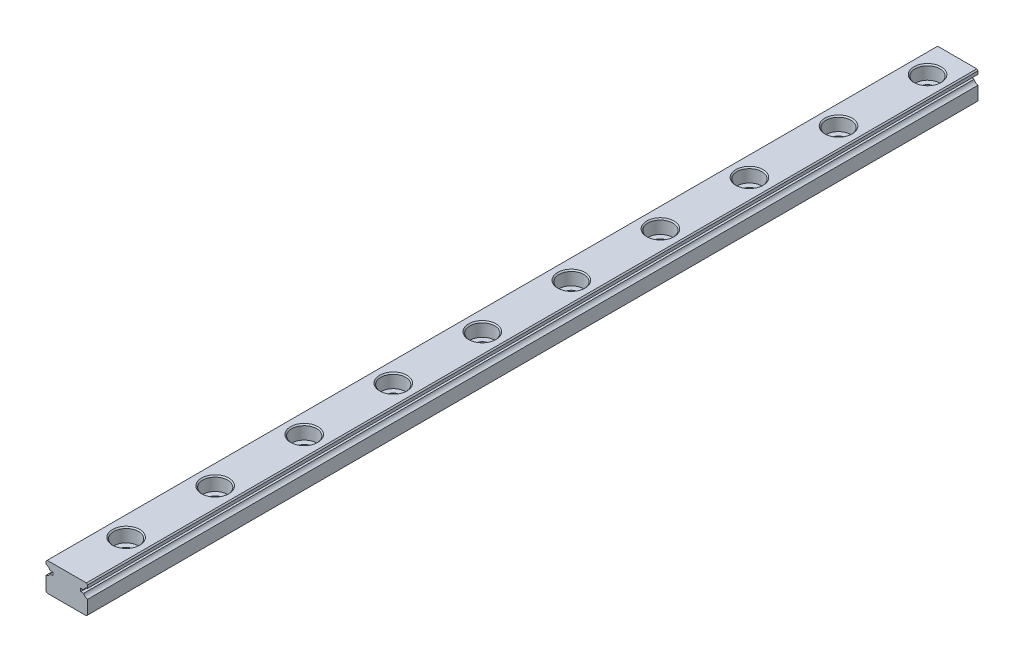
SolidWorks part; units mm, degrees
ref_plane "Спереди" through (0, 0, 0) normal (0, 0, 1) x (1, 0, 0)
ref_plane "Сверху" through (0, 0, 0) normal (0, 1, 0) x (1, 0, 0)
ref_plane "Справа" through (0, 0, 0) normal (1, 0, 0) x (0, 0, -1)
sketch "Sketch1" plane through (0, 0, 0) normal (0, 0, 1) x (1, 0, 0)
  line L0 (0, 0) -> (0, 4.3706) construction
  line L1 (-3.3, -2.4) -> (3.3, -2.4)
  line L2 (-3.5, -2.2) -> (-3.5, 0.1063)
  line L3 (-3.3, 2.4) -> (3.3, 2.4)
  line L4 (3.5, -2.2) -> (3.5, 0.1063)
  line L5 (-3.5, -2.4) -> (3.5, 2.4) construction
  line L6 (-3.5, 2.4) -> (3.5, -2.4) construction
  line L7 (-3.5, 1.6937) -> (-3.5, 2.2)
  line L8 (3.5, 1.6937) -> (3.5, 2.2)
  line L9 (-3.5, -2.2) -> (-3.3, -2.4)
  line L10 (3.3, -2.4) -> (3.5, -2.2)
  line L11 (3.3, 2.4) -> (3.5, 2.2)
  line L12 (-3.5, 2.2) -> (-3.3, 2.4)
  line L13 (2.8401, 0.65) -> (2.3401, 0.65)
  line L14 (-2.8401, 0.65) -> (-2.3401, 0.65)
  line L15 (2.3401, 0.65) -> (2.3401, 1.15)
  line L16 (-2.8401, 1.15) -> (-2.3401, 1.15)
  line L17 (-2.3401, 0.65) -> (-2.3401, 1.15)
  line L18 (2.8401, 1.15) -> (2.3401, 1.15)
  arc A0 (-3.5, 1.6937) -> (-2.8401, 1.15) centre (-3.6, 0.9) cw
  arc A1 (3.5, 1.6937) -> (2.8401, 1.15) centre (3.6, 0.9) ccw
  arc A2 (-2.8401, 0.65) -> (-3.5, 0.1063) centre (-3.6, 0.9) cw
  arc A3 (2.8401, 0.65) -> (3.5, 0.1063) centre (3.6, 0.9) ccw
  point P0 (0, 0)
  dimension "D4" = 0.8
  dimension "D5" = 0.1
  dimension "D1" = 7
  dimension "D2" = 4.8
  dimension "D3" = 1.5
  dimension "D6" = 0.5
  dimension "D7" = 0.5
extrude "Extrude1" add sketch "Sketch1" along normal blind 150
sketch "Sketch2" plane through (0, 2.4, 0) normal (0, 1, 0) x (1, 0, 0)
  line L0 (0, 0) -> (0, -5) construction
  circle A0 centre (0, -5) radius 1.2
  circle A1 centre (0, -5) radius 2.1
  dimension "D1" = 2.4
  dimension "D2" = 4.2
  dimension "D3" = 5
extrude "Extrude2" cut sketch "Sketch2" against normal up to next contours A0 region at (0, 2.4, 5)
extrude "Extrude4" cut sketch "Sketch" against normal blind 2.3
sketch "Sketch" plane through (0, 2.4, 0) normal (0, 1, 0) x (1, 0, 0) same geometry as "Sketch2"
chamfer "Chamfer1" distance 0.2 angle 45 2 edges at (0, -2.4, 6.2) (0, 2.4, 7.1)
pattern_linear "LPattern1" count 10 spacing 15 along (0, 0, 1) of "Extrude4", "Chamfer1", "Extrude2"
sketch "Sketch6" plane through (0, 2.4, 0) normal (0, 1, 0) x (1, 0, 0)
